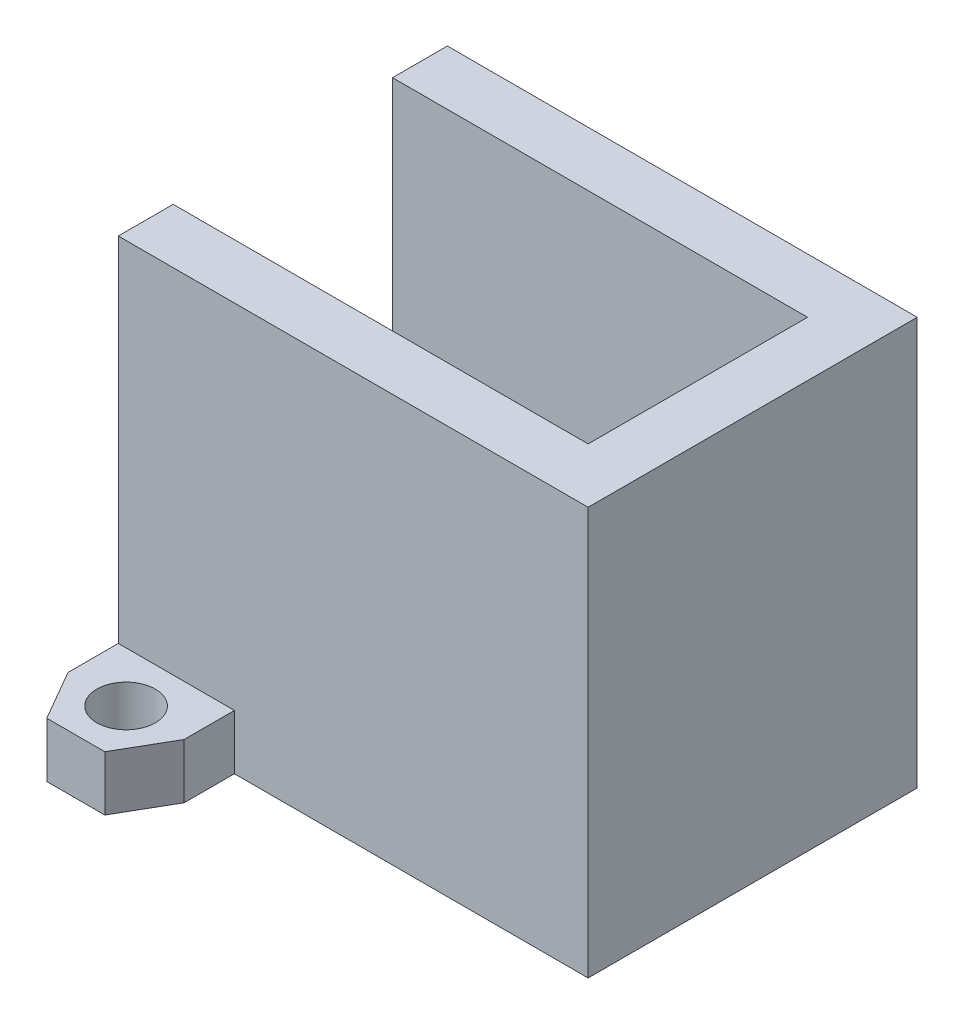
SolidWorks part; units mm, degrees
ref_plane "Front Plane" through (0, 0, 0) normal (0, 0, 1) x (1, 0, 0)
ref_plane "Top Plane" through (0, 0, 0) normal (0, 1, 0) x (1, 0, 0)
ref_plane "Right Plane" through (0, 0, 0) normal (1, 0, 0) x (0, 0, -1)
sketch "Sketch1" plane through (0, 0, 0) normal (0, 1, 0) x (1, 0, 0)
  line L0 (-11.35, 9) -> (14.35, 9)
  line L1 (-11.35, 6) -> (11.35, 6)
  line L3 (-11.35, -6) -> (11.35, -6)
  line L4 (11.35, 6) -> (11.35, -6)
  line L5 (-11.35, 6) -> (11.35, -6) construction
  line L6 (-11.35, -6) -> (11.35, 6) construction
  line L7 (14.35, 9) -> (14.35, -9)
  line L8 (-11.35, -9) -> (14.35, -9)
  line L10 (-11.35, 9) -> (-11.35, 6)
  line L11 (-14.35, 9) -> (14.35, 9) construction
  line L12 (-14.35, 9) -> (-14.35, -9) construction
  line L13 (-14.35, -9) -> (14.35, -9) construction
  line L14 (-11.35, -6) -> (-11.35, -9)
  line L15 (-11.35, 6) -> (-11.35, -6) construction
  line L16 (-11.35, 11.75) -> (-11.35, 9)
  line L17 (-6.5869, 9) -> (-4.9991, 11.75)
  line L18 (-4.9991, 11.75) -> (-6.5869, 14.5)
  line L19 (-6.5869, 14.5) -> (-9.7623, 14.5)
  line L20 (-9.7623, 14.5) -> (-11.35, 11.75)
  line L21 (-11.35, 11.75) -> (-9.7623, 9)
  line L22 (-9.7623, 9) -> (-6.5869, 9)
  line L23 (-4.9991, 11.75) -> (-4.9991, 9)
  line L24 (-29.5726, 0) -> (26.4244, 0) construction
  line L25 (-4.9991, -11.75) -> (-4.9991, -9)
  line L26 (-11.35, -11.75) -> (-11.35, -9)
  line L27 (-9.7623, -9) -> (-6.5869, -9)
  line L28 (-11.35, -11.75) -> (-9.7623, -9)
  line L29 (-9.7623, -14.5) -> (-11.35, -11.75)
  line L30 (-6.5869, -14.5) -> (-9.7623, -14.5)
  line L31 (-4.9991, -11.75) -> (-6.5869, -14.5)
  line L32 (-6.5869, -9) -> (-4.9991, -11.75)
  circle A0 centre (-8.1746, 11.75) radius 2.75 construction
  circle A1 centre (-8.1746, 11.75) radius 1.6
  circle A2 centre (-8.1746, -11.75) radius 1.6
  point P0 (0, 0)
  dimension "D5" = 3.2
  dimension "D1" = 12
  dimension "D2" = 22.7
  dimension "D4" = 5.5
  dimension "D3" = 3
extrude "Boss-Extrude1" add sketch "Sketch1" along normal blind 3 contours L26 L28 L8 | L32 L8 L28 L29 L30 L31 A2 | L8 L32 L25 | L21 L16 L0 | L20 L21 L0 L17 L18 L19 A1 | L23 L17 L0 region at (-10.8208, 0, -9.9167) region at (-10.4834, 0, -10.417) region at (-5.5284, 0, -9.9167) region at (-10.8208, 0, 9.9167) region at (-5.5284, 0, 9.9167) region at (-8.1746, 0, 9.084)
extrude "Boss-Extrude2" add sketch "Sketch1<3>" along normal blind 22.3 contours L3 L14 L8 L7 L0 L10 L1 L4 region at (-10.5561, 0, -8.6862)
sketch "Sketch1<3>" plane through (0, 0, 0) normal (0, 1, 0) x (1, 0, 0) same geometry as "Sketch1"
